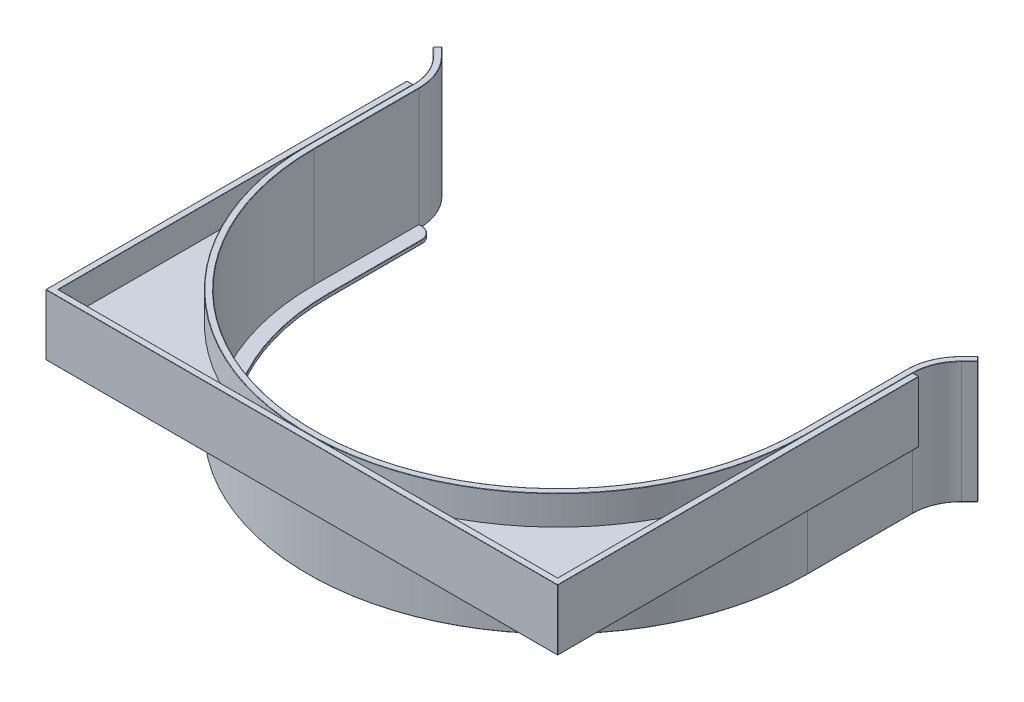
SolidWorks part; units mm, degrees
material "1060 Alloy"
ref_plane "Front Plane" through (0, 0, 0) normal (0, 0, 1) x (1, 0, 0)
ref_plane "Top Plane" through (0, 0, 0) normal (0, 1, 0) x (1, 0, 0)
ref_plane "Right Plane" through (0, 0, 0) normal (1, 0, 0) x (0, 0, -1)
sketch "Sketch1" plane through (0, 0, 0) normal (0, 1, 0) x (1, 0, 0)
  line L8 (205, 0) -> (200, 0)
  line L9 (-205, 0) -> (-200, 0)
  arc A0 (-200, 0) -> (200, 0) centre (0, 0) ccw
  arc A1 (-205, 0) -> (205, 0) centre (0, 0) ccw
  circle A2 centre (0, 0) radius 205 construction
  circle A3 centre (0, 0) radius 200 construction
  dimension "D1" = 400
  dimension "D2" = 5
extrude "Boss-Extrude1" add sketch "Sketch1" along normal blind 100 contours A1 L8 A0 L9 region at (0, 0, 200.4161)
sketch "Sketch2" plane through (0, 0, 0) normal (0, 1, 0) x (1, 0, 0)
  line L0 (-223.5355, 121.4645) -> (-216.7157, 114.6447)
  line L1 (-223.5355, 121.4645) -> (-220, 125)
  line L2 (-220, 125) -> (-213.1802, 118.1802)
  line L3 (-205, 86.3604) -> (-205, 0)
  line L4 (-200, 0) -> (-200, 86.3604)
  line L5 (-200, 0) -> (-205, 0)
  arc A0 (-216.7157, 114.6447) -> (-205, 86.3604) centre (-245, 86.3604) cw
  arc A2 (-213.1802, 118.1802) -> (-200, 86.3604) centre (-245, 86.3604) cw
  arc A5 (-205, 0) -> (205, 0) centre (0, 0) ccw construction
  dimension "D4" = 135
  dimension "D3" = 40
  dimension "D2" = 125
  dimension "D1" = 20
extrude "Boss-Extrude2" add sketch "Sketch2" along normal up to surface (100 mm away) up to face at (0, 100, 101.25)
mirror "Mirror1" about plane through (0, 0, 0) normal (1, 0, 0) of "Boss-Extrude2"
sketch "Sketch3" plane through (0, 0, 0) normal (0, 1, 0) x (1, 0, 0)
  line L0 (-200, 0) -> (-200, 86.3604)
  line L1 (200, 0) -> (200, 86.3604)
  line L2 (-200, 86.3604) -> (-188, 86.3604)
  line L3 (-188, 86.3604) -> (-188, 0)
  line L4 (200, 86.3604) -> (188, 86.3604)
  line L5 (188, 86.3604) -> (188, 0)
  arc A0 (-200, 0) -> (200, 0) centre (0, 0) ccw construction
  arc A1 (-200, 0) -> (200, 0) centre (0, 0) ccw
  arc A2 (-188, 0) -> (188, 0) centre (0, 0) ccw
  dimension "D1" = 376
extrude "Boss-Extrude3" add sketch "Sketch3" along normal blind 3
fillet "Fillet1" radius 10 2 edges at (-188, 1.5, -86.3604) (188, 1.5, -86.3604)
ref_plane "Plane1" through (0, 40, 0) normal (0, 1, 0) x (1, 0, 0)
ref_plane "Plane2" through (0, 100, 0) normal (0, 1, 0) x (1, 0, 0)
sketch "Sketch4" plane through (0, 100, 0) normal (0, 1, 0) x (1, 0, 0)
  line L0 (-205, 86.3604) -> (-205, -205)
  line L1 (-205, -205) -> (205, -205)
  line L2 (205, -205) -> (205, 86.3604)
  line L3 (-210, 86.3604) -> (-210, -210)
  line L4 (-210, -210) -> (210, -210)
  line L5 (210, -210) -> (210, 86.3604)
  line L6 (-205, 86.3604) -> (-210, 86.3604)
  line L7 (205, 86.3604) -> (210, 86.3604)
  arc A0 (-205, 0) -> (205, 0) centre (0, 0) ccw construction
  dimension "D1" = 5
extrude "Boss-Extrude4" add sketch "Sketch4" against normal blind 50 separate body
sketch "Sketch5" plane through (0, 0, 0) normal (1, 0, 0) x (0, 0, -1)
  line L1 (86.3604, 50) -> (86.3604, 100) construction
  line L2 (-210, 100) -> (86.3604, 100) construction
  point P0 (61.3604, 90)
  point P1 (-173.6396, 90)
  dimension "D1" = 25
  dimension "D2" = 235
  dimension "D3" = 10
ref_axis "Axis1" through (-228.7756, 90, 173.6396) along (1, 0, 0)
ref_axis "Axis2" through (-220.8647, 90, -61.3604) along (1, 0, 0)
ref_plane "Plane3" through (0, 75, 0) normal (0, 1, 0) x (1, 0, 0)
sketch "Sketch6" plane through (0, 75, 0) normal (0, 1, 0) x (1, 0, 0)
  line L0 (205, -205) -> (-205, -205) construction
  line L1 (-205, -205) -> (-205, 86.3604) construction
  line L2 (-49.5984, -205) -> (-205, -205)
  line L3 (-205, -205) -> (-205, -49.5984)
  arc A0 (-205, 0) -> (205, 0) centre (0, 0) ccw construction
  arc A1 (-199.0865, -48.883) -> (-48.883, -199.0865) centre (0, 0) ccw
  arc A2 (-48.883, -199.0865) -> (-49.5984, -205) centre (-49.5984, -202) cw
  arc A3 (-199.0865, -48.883) -> (-205, -49.5984) centre (-202, -49.5984) ccw
  dimension "D1" = 3
extrude "Boss-Extrude10" add sketch "Sketch6" along normal mid plane 2 separate body contours A1 A2 L2 L3 A3
mirror "Mirror3" about plane through (0, 0, 0) normal (1, 0, 0) of bodies 107
fillet "Fillet2" radius 0.3 47 edges at (-199, 0, -86.3604) (-190.9289, 0, -83.4315) (-188, 0, -38.1802) (0, 0, 188) (188, 0, -38.1802) (199, 0, -86.3604) (199, 3, -86.3604) (-199, 3, -86.3604) (-190.9289, 3, -83.4315) (-188, 3, -38.1802) (0, 3, 188) (188, 3, -38.1802) (-220.1256, 0, -118.0546) (-208.0448, 0, -101.6677) (-205, 0, -43.1802) (0, 0, 205) (205, 0, -43.1802) (220.1256, 100, -118.0546) (208.0448, 100, -101.6677) (205, 100, -43.1802) (0, 100, 205) (-205, 100, -43.1802) (-203.4254, 0, -103.5811) (203.4254, 0, -103.5811) (-216.5901, 100, -121.5901) (-203.4254, 100, -103.5811) (-200, 100, -43.1802) (216.5901, 100, -121.5901) (203.4254, 100, -103.5811) (200, 100, -43.1802) (190.9289, 0, -83.4315) (190.9289, 3, -83.4315) (208.0448, 0, -101.6677) (220.1256, 0, -118.0546) (221.7678, 0, -123.2322) (223.5355, 50, -121.4645) (221.7678, 100, -123.2322) (-220.1256, 100, -118.0546) (-208.0448, 100, -101.6677) (-221.7678, 100, -123.2322) (-223.5355, 50, -121.4645) (-221.7678, 0, -123.2322) (-216.5901, 0, -121.5901) (-220, 50, -125) (216.5901, 0, -121.5901) (220, 50, -125) (0, 100, 200)
fillet "Fillet3" radius 0.2 22 edges at (0, 100, 205) (205, 100, 59.3198) (207.5, 100, -86.3604) (-207.5, 100, -86.3604) (210, 75, -86.3604) (210, 100, 61.8198) (-205, 75, -86.3604) (-205, 75, 205) (-205, 100, 59.3198) (-210, 75, -86.3604) (-210, 100, 61.8198) (210, 75, 210) (-210, 75, 210) (0, 100, 210) (-210, 50, 61.8198) (0, 50, 210) (210, 50, 61.8198) (207.5, 50, -86.3604) (205, 50, 59.3198) (0, 50, 205) (-205, 50, 59.3198) (-207.5, 50, -86.3604)
